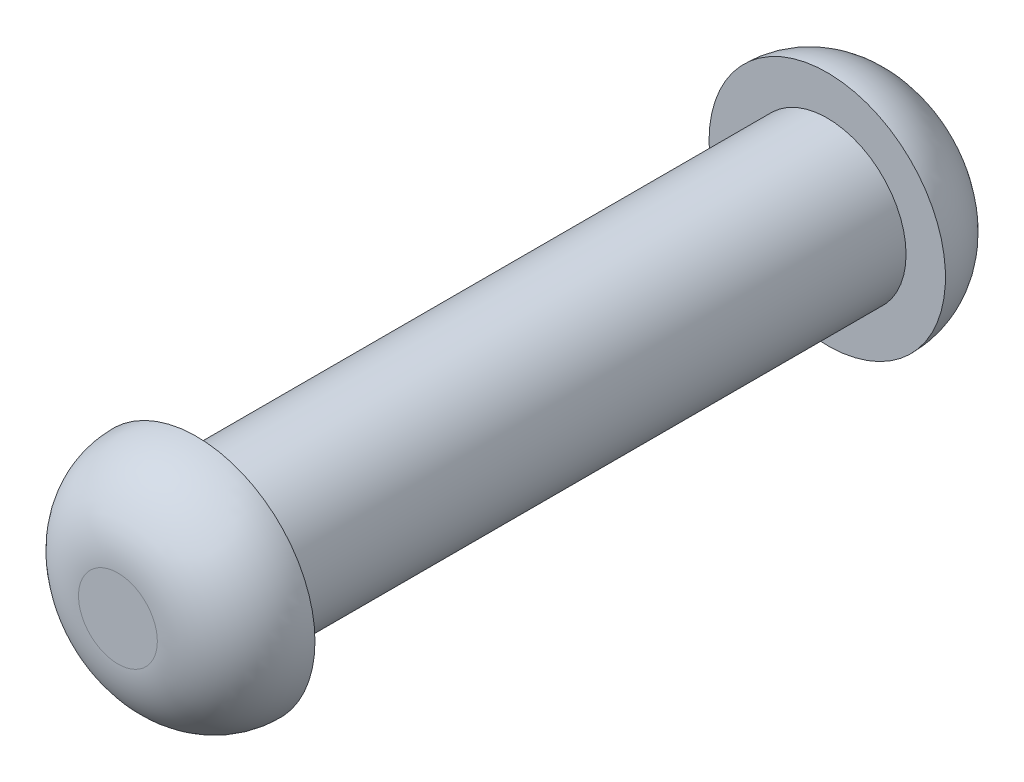
SolidWorks part; units mm, degrees
ref_plane "Ön Düzlem" through (0, 0, 0) normal (0, 0, 1) x (1, 0, 0)
ref_plane "Üst Düzlem" through (0, 0, 0) normal (0, 1, 0) x (1, 0, 0)
ref_plane "Sağ Düzlem" through (0, 0, 0) normal (1, 0, 0) x (0, 0, -1)
sketch "Çizim1" plane through (0, 0, 0) normal (0, 0, 1) x (1, 0, 0)
  circle A0 centre (0, 0) radius 5
extrude "Yükseklik-Ekstrüzyon1" add sketch "Çizim1" along normal blind 40
sketch "Çizim2" plane through (0, 0, 40) normal (0, 0, 1) x (1, 0, 0)
  circle A0 centre (0, 0) radius 7.5
extrude "Yükseklik-Ekstrüzyon2" add sketch "Çizim2" along normal blind 5
fillet "Radyus1" radius 5 1 edges at (7.5, 0, 45)
sketch "Çizim3" plane through (0, 0, 0) normal (0, 0, -1) x (-1, 0, 0)
  circle A0 centre (0, 0) radius 7.5
extrude "Yükseklik-Ekstrüzyon3" add sketch "Çizim3" along normal blind 5
fillet "Radyus2" radius 5 1 edges at (-7.5, 0, -5)
